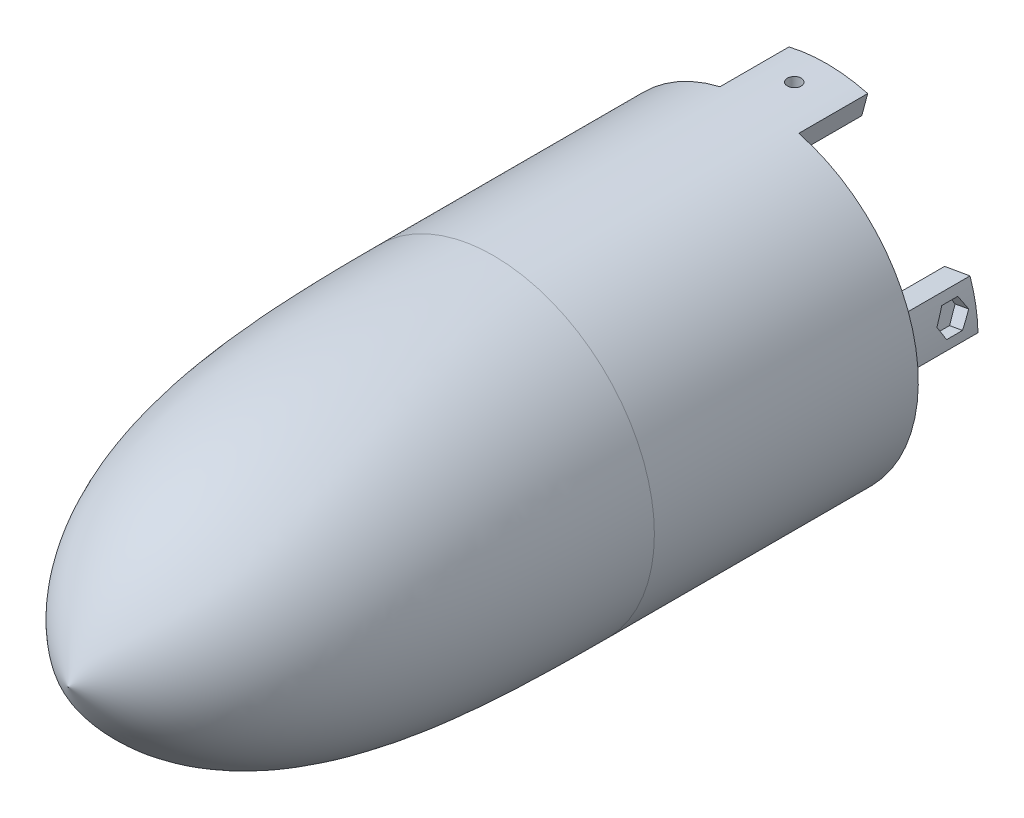
SolidWorks part; units mm, degrees
ref_plane "Front Plane" through (0, 0, 0) normal (0, 0, 1) x (1, 0, 0)
ref_plane "Top Plane" through (0, 0, 0) normal (0, 1, 0) x (1, 0, 0)
ref_plane "Right Plane" through (0, 0, 0) normal (1, 0, 0) x (0, 0, -1)
sketch "Sketch4" plane through (0, 0, 0) normal (0, 0, 1) x (1, 0, 0)
  circle A1 centre (0, 0) radius 35
  dimension "D1" = 70
extrude "Boss-Extrude10" add sketch "Sketch4" along normal blind 150
sketch "Sketch24" plane through (0, 0, 0) normal (1, 0, 0) x (0, 0, -1)
  line L0 (-50, 35) -> (-50, -35)
  line L1 (0, 35) -> (-150, 35) construction
  line L2 (-150, -35) -> (0, -35) construction
  line L3 (-150, 35) -> (-150, -35) construction
  line L4 (-150, 0) -> (-163.533, 0)
  line L5 (-163.533, 0) -> (-163.533, 49.8581)
  line L6 (-163.533, 49.8581) -> (-50, 49.8581)
  line L7 (-50, 49.8581) -> (-50, 35)
  line L8 (-150, 0) -> (3.4372, 0) construction
  spline S0 degree 3 poles (-50, 35) (-89.421, 35) (-134.1291, 35.776) (-150, 0) knots 0 0 0 0 1 1 1 1
  point P14 (-150, 0)
  point P16 (-150, 0)
  point P17 (0, 0)
revolve "Cut-Revolve5" cut sketch "Sketch24" angle 360 about L8 region at (0, 34.4969, 121.1785)
shell "Shell11" thickness 2 removed face at (35, 0, 0)
sketch "Sketch25" plane through (0, 0, 0) normal (0, 0, 1) x (1, 0, 0)
  line L0 (0, 0) -> (0, -39.6781) construction
  line L1 (0, 0) -> (-55.2543, 9.7428) construction
  line L2 (0, 0) -> (59.6974, 10.5263) construction
  line L3 (32.9917, 0.7402) -> (27.4581, -0.2355)
  line L4 (27.4581, -0.2355) -> (25.7216, 9.6125)
  line L5 (25.7216, 9.6125) -> (31.2552, 10.5883)
  line L6 (-31.2552, 10.5883) -> (-25.7216, 9.6125)
  line L7 (-25.7216, 9.6125) -> (-27.4581, -0.2355)
  line L8 (-27.4581, -0.2355) -> (-32.9917, 0.7402)
  line L9 (-5, -32.619) -> (-5, -27)
  line L10 (-5, -27) -> (5, -27)
  line L11 (5, -27) -> (5, -32.619)
  line L12 (0, 0) -> (0, 39.4018) construction
  line L13 (-6.8514, 29.2072) -> (-8.146, 34.0388)
  line L14 (7.7022, 28.9944) -> (8.9963, 33.824)
  line L15 (7.7022, 28.9944) -> (-6.8514, 29.2072)
  circle A0 centre (0, 0) radius 33 construction
  arc A1 (32.9917, 0.7402) -> (31.2552, 10.5883) centre (0, 0) ccw
  arc A2 (-31.2552, 10.5883) -> (-32.9917, 0.7402) centre (0, 0) ccw
  arc A3 (-5, -32.619) -> (5, -32.619) centre (0, 0) ccw
  circle A4 centre (0, 0) radius 33 construction
  circle A6 centre (0, 0) radius 35
  arc A7 (8.9963, 33.824) -> (-8.146, 34.0388) centre (0, 0) ccw
  arc A8 (32.9917, 0.7402) -> (31.2552, 10.5883) centre (0, 0) ccw
  arc A9 (-5, -32.619) -> (5, -32.619) centre (0, 0) ccw
  arc A10 (-31.2552, 10.5883) -> (-32.9917, 0.7402) centre (0, 0) ccw
  arc A12 (-29.9992, 0.2125) -> (-5, -29.5804) centre (0, 0) ccw
  point P18 (26.5898, 4.6885)
  point P23 (-26.5898, 4.6885)
  point P29 (0, -27)
  dimension "D1" = 100
  dimension "D2" = 100
  dimension "D3" = 10
  dimension "D4" = 27
  dimension "D5" = 27
  dimension "D6" = 27
  dimension "D7" = 10
  dimension "D8" = 10
  dimension "D12" = 39.4018
  dimension "D10" = 15
  dimension "D11" = 15
  dimension "D9" = 0
extrude "Boss-Extrude11" add sketch "Sketch25" along normal up to next contours L3 A1 L5 L4 | L6 A2 L8 L7 | L9 A3 L11 L10 region at (29.4829, 5.1986, 0) region at (0, -29.9377, 0) region at (-29.4829, 5.1986, 0)
extrude "Boss-Extrude12" add sketch "Sketch25<2>" against normal blind 15 contours L3 A1 L5 L4 | L9 A3 L11 L10 | L6 A2 L8 L7 | A7 L13 L15 L14 region at (29.4829, 5.1986, 0) region at (0, -29.9377, 0) region at (-29.4829, 5.1986, 0)
sketch "Sketch25<2>" plane through (0, 0, 0) normal (0, 0, 1) x (1, 0, 0) same geometry as "Sketch25"
ref_plane "Plane3" through (32.4987, 5.7304, 0) normal (-0.9848, -0.1736, 0) x (0, 0, 1)
ref_plane "Plane4" through (-32.4987, 5.7304, 0) normal (0.9848, -0.1736, 0) x (0, 0, -1)
ref_plane "Plane5" through (0, -33, 0) normal (0, 1, 0) x (1, 0, 0)
sketch "Sketch26" plane through (32.4987, 5.7304, 0) normal (-0.9848, -0.1736, 0) x (0, 0, 1)
  line L1 (-8.2688, -3.0005) -> (-6.5359, -0.0009)
  line L2 (-6.5359, -0.0009) -> (-8.2671, 2.9995)
  line L3 (-8.2671, 2.9995) -> (-11.7312, 3.0005)
  line L4 (-11.7312, 3.0005) -> (-13.4641, 0.0009)
  line L5 (-13.4641, 0.0009) -> (-11.7329, -2.9995)
  line L6 (-11.7329, -2.9995) -> (-8.2688, -3.0005)
  circle A0 centre (-10, 0) radius 3 construction
  dimension "D1" = 10
  dimension "D2" = 6
extrude "Cut-Extrude7" cut sketch "Sketch26" along normal blind 3
sketch "Sketch27" plane through (-32.4987, 5.7304, 0) normal (0.9848, -0.1736, 0) x (0, 0, -1)
  line L1 (11.6993, -3.0187) -> (13.4639, -0.0377)
  line L2 (13.4639, -0.0377) -> (11.7646, 2.981)
  line L3 (11.7646, 2.981) -> (8.3007, 3.0187)
  line L4 (8.3007, 3.0187) -> (6.5361, 0.0377)
  line L5 (6.5361, 0.0377) -> (8.2354, -2.981)
  line L6 (8.2354, -2.981) -> (11.6993, -3.0187)
  circle A0 centre (10, 0) radius 3 construction
  dimension "D1" = 10
  dimension "D2" = 6
extrude "Cut-Extrude8" cut sketch "Sketch27" along normal blind 3
sketch "Sketch28" plane through (0, -33, 0) normal (0, 1, 0) x (1, 0, 0)
  line L1 (0, 13.4641) -> (-3, 11.7321)
  line L2 (-3, 11.7321) -> (-3, 8.2679)
  line L3 (-3, 8.2679) -> (0, 6.5359)
  line L4 (0, 6.5359) -> (3, 8.2679)
  line L5 (3, 8.2679) -> (3, 11.7321)
  line L6 (3, 11.7321) -> (0, 13.4641)
  circle A0 centre (0, 10) radius 3 construction
  dimension "D1" = 10
  dimension "D2" = 6
extrude "Cut-Extrude9" cut sketch "Sketch28" along normal blind 3
sketch "Sketch29" plane through (0, 0, 0) normal (0, 0, 1) x (1, 0, 0)
  line L0 (28.8617, 16) -> (-28.8617, 16)
  circle A0 centre (0, 0) radius 33 construction
  arc A1 (28.8617, 16) -> (-28.8617, 16) centre (0, 0) ccw
  dimension "D1" = 16
extrude "Boss-Extrude13" add sketch "Sketch29" along normal blind 15
sketch "Sketch30" plane through (0, 0, 0) normal (0, 0, -1) x (-1, 0, 0)
  line L0 (-24.367, 17.5) -> (24.367, 17.5)
  arc A1 (24.367, 17.5) -> (-24.367, 17.5) centre (0, 0) ccw
  dimension "D2" = 60
  dimension "D1" = 17.5
extrude "Cut-Extrude10" cut sketch "Sketch30" against normal up to next
fillet "Fillet4" radius 8 1 edges at (0, 33, 15)
sketch "Sketch32" plane through (0, 0, 0) normal (0, 1, 0) x (1, 0, 0)
  line L0 (-6.8514, 0) -> (-24.367, 0) construction
  line L1 (-6.8514, 0) -> (-24.367, 0) construction
  circle A0 centre (0, 8) radius 1.5
  dimension "D1" = 3
  dimension "D2" = 8
extrude "Cut-Extrude11" cut sketch "Sketch32" along normal through all contours A0
equation "\"fuse_diam\"= 0.07"
equation "\"fuse_rad\"= 0.035"
equation "\"battery_length\"= 0.076"
equation "\"battery_width\"= 0.034"
equation "\"battery_height\"= 0.051"
equation "\"bat_bay_length\"= 0.096"
equation "\"shell\"= 0.002"
equation "\"wing_shelf\"= 0.0175"
equation "\"chord_length\"= 0.089"
equation "\"tail_length\"= 0.26532000000000006"
equation "\"tail_diam\"= 0.035"
equation "\"connector\"= 0.06633000000000001"
equation "\"D1@Sketch4\"=\"fuse_diam\""
equation "\"D1@Sketch24\"=.05"
equation "\"D4@Sketch25\"=\"fuse_rad\"-.008"
equation "\"D5@Sketch25\"=\"fuse_rad\"-0.008"
equation "\"D6@Sketch25\"=\"fuse_rad\"-0.008"
equation "\"D1@Sketch29\"=\"wing_shelf\" -0.0015"
equation "\"D2@Sketch30\"=\"fuse_diam\"-0.01"
equation "\"D1@Sketch30\"=\"wing_shelf\""
